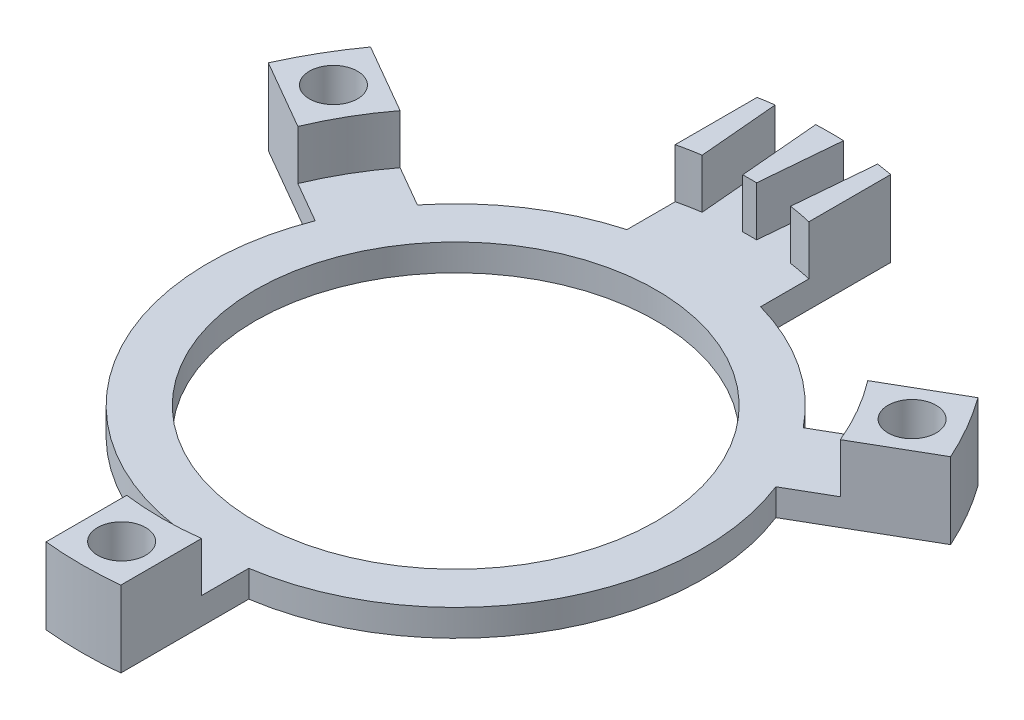
SolidWorks part; units mm, degrees
material "Delrin 2700 NC010, Low Viscosity Acetal Copolymer (SS)"
ref_plane "Front" through (0, 0, 0) normal (0, 0, 1) x (1, 0, 0)
ref_plane "Top" through (0, 0, 0) normal (0, 1, 0) x (1, 0, 0)
ref_plane "Right" through (0, 0, 0) normal (1, 0, 0) x (0, 0, -1)
sketch "Sketch1" plane through (0, 0, 0) normal (0, 0, 1) x (1, 0, 0)
  line L0 (0, 0) -> (14, 0)
  line L1 (14, 0) -> (14, 2.85)
  line L2 (14, 2.85) -> (11, 2.85)
  line L3 (11, 2.85) -> (11, 1)
  line L4 (11, 1) -> (0, 1)
  line L5 (0, 1) -> (0, 0)
  line L6 (7.5, 1) -> (7.5, 0)
  dimension "D1" = 11
  dimension "D2" = 3
  dimension "D3" = 1.85
  dimension "D4" = 1
  dimension "D5" = 7.5
revolve "Revolve1" add sketch "Sketch1" angle 360 about L5 region at (11.556, 1.1563, 0)
sketch "Sketch2" plane through (0, 2.85, 0) normal (0, 1, 0) x (1, 0, 0)
  line L0 (0, 0) -> (0, 14) construction
  line L1 (0, 0) -> (1.2202, 13.9467)
  line L2 (1.9175, 13.8857) -> (0.5228, 14.0077)
  line L3 (0.6973, -0.061) -> (-0.6973, 0.061)
  line L4 (1.9175, 13.8857) -> (0.6973, -0.061)
  line L5 (0.5228, 14.0077) -> (-0.6973, 0.061)
  line L6 (-1.9175, 13.8857) -> (-0.6973, -0.061)
  line L7 (0.6973, 0.061) -> (-0.6973, -0.061)
  line L8 (-0.5228, 14.0077) -> (0.6973, 0.061)
  line L9 (-0.5228, 14.0077) -> (-1.9175, 13.8857)
  line L10 (0, 0) -> (-0.6973, 0.061) construction
  line L11 (0, 0) -> (-0.6973, -0.061) construction
  circle A0 centre (0, 0) radius 14 construction
  point P0 (0, 8.0316)
  point P10 (1.2202, 13.9467)
  point P15 (0, 0)
  circle M7 centre (0, 0) radius 11
  circle M8 centre (0, 0) radius 14
  dimension "D2" = 1.4
  dimension "D4" = 10
  dimension "D3" = 2
extrude "Cut-Extrude1" cut sketch "Sketch2" against normal up to surface (1.85 mm away) contours L5 L1 M8 M7 | L4 L1 M8 M7 | L8 L6 M8 M7 region at (0.7401, 2.85, -12.4763) region at (1.4376, 2.85, -12.4153) region at (-1.0889, 2.85, -12.4458) up to face at (-7.5, 1, 0)
sketch "Sketch4" plane through (0, 2.85, 0) normal (0, 1, 0) x (1, 0, 0)
  line L0 (0, 0) -> (0, -12.5) construction
  line L2 (1.4, 0) -> (1.4, -14.3419)
  line L3 (1.4, -14.3419) -> (-1.4, -14.3419)
  line L4 (-1.4, -14.3419) -> (-1.4, 0)
  line L6 (-1.4, 0) -> (1.4, 0)
  line L7 (-11.7204, 8.3834) -> (0.7, 1.2124)
  line L8 (0.7, 1.2124) -> (-0.7, -1.2124)
  line L9 (-0.7, -1.2124) -> (-13.1204, 5.9585)
  line L10 (-13.1204, 5.9585) -> (-11.7204, 8.3834)
  line L11 (13.1204, 5.9585) -> (0.7, -1.2124)
  line L12 (0.7, -1.2124) -> (-0.7, 1.2124)
  line L13 (-0.7, 1.2124) -> (11.7204, 8.3834)
  line L14 (11.7204, 8.3834) -> (13.1204, 5.9585)
  line L16 (-2.5, 14) -> (2.5, 14)
  line L17 (-2.5, 14) -> (-2.5, 8.9058)
  line L18 (2.5, 14) -> (2.5, 8.9058)
  circle A0 centre (0, -12.5) radius 0.9
  circle A1 centre (-10.8253, 6.25) radius 0.9
  circle A2 centre (10.8253, 6.25) radius 0.9
  circle A3 centre (0, 0) radius 7.5 construction
  arc A4 (-1.6541, 10.8749) -> (1.6541, 10.8749) centre (0, 0) ccw construction
  arc A5 (-1.916, 13.8683) -> (1.916, 13.8683) centre (0, 0) ccw construction
  circle A6 centre (0, 0) radius 7.5
  arc A7 (-1.6541, 10.8749) -> (1.6541, 10.8749) centre (0, 0) ccw
  arc A8 (-1.916, 13.8683) -> (1.916, 13.8683) centre (0, 0) ccw
  circle A9 centre (0, 0) radius 9.25
  arc A11 (0.5213, 13.9903) -> (-0.5213, 13.9903) centre (0, 0) ccw construction
  point P22 (0, 14)
  point P23 (0, 0)
  point P38 (0, 14)
  arc M4 (1.6541, 10.8749) -> (-1.6541, 10.8749) centre (0, 0) cw
  arc M6 (-1.916, 13.8683) -> (1.916, 13.8683) centre (0, 0) ccw
  dimension "D2" = 1.8
  dimension "D5" = 18.5
  dimension "D1" = 12.5
  dimension "D4" = 2.8
  dimension "D7" = 5
  dimension "D3" = 3
  dimension "D6" = 3
extrude "Cut-Extrude2" cut sketch "Sketch4" against normal through all contours A1 | A2 | A0 | L9 L4 M4 M6 | L11 L2 M6 M4 | L18 L13 M6 M4 | L17 L7 M6 M4 | A9 L9 L4 M4 | A9 L17 L7 M4 | A9 L13 L18 M4 | A9 L2 L11 M4 region at (7.1544, 2.85, 6.1423) region at (9.7287, 2.85, 5.6168) region at (-1.5794, 2.85, 10.027) region at (5.4597, 2.85, -8.3557) region at (-1.6337, 2.85, 12.4202) region at (6.6173, 2.85, -10.3726) region at (-5.4597, 2.85, -8.3557) region at (-6.6173, 2.85, -10.3726) region at (0, 2.85, 12.5) region at (-10.8253, 2.85, -6.25) region at (10.8253, 2.85, -6.25)
